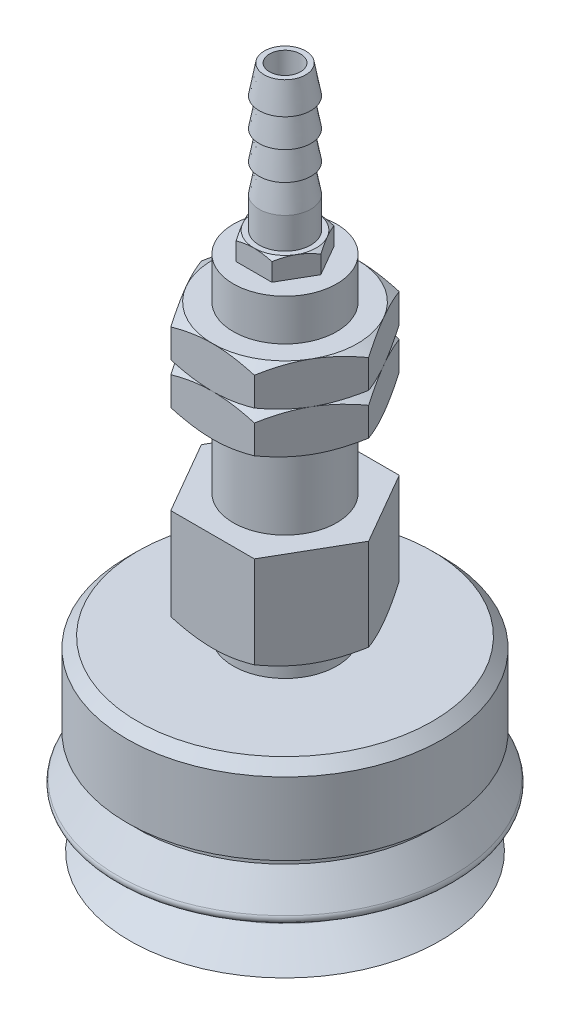
SolidWorks part; units mm, degrees
ref_plane "前视基准面" through (0, 0, 0) normal (0, 0, 1) x (1, 0, 0)
ref_plane "上视基准面" through (0, 0, 0) normal (0, 1, 0) x (1, 0, 0)
ref_plane "右视基准面" through (0, 0, 0) normal (1, 0, 0) x (0, 0, -1)
sketch "草图1" plane through (0, 0, 0) normal (0, 0, 1) x (1, 0, 0)
  line L0 (0, 17.9034) -> (0, 13.7034) construction
  line L1 (-2, 66) -> (2, 66)
  line L4 (-2.5, 63.25) -> (-2, 63.25)
  line L5 (-2.5, 63.25) -> (-2, 66)
  line L7 (14.25, 9) -> (14.25, 10)
  line L8 (14.25, 10) -> (15.25, 10)
  line L9 (-2.5, 60.5) -> (-2, 60.5)
  line L10 (-2.5, 60.5) -> (-2, 63.25)
  line L13 (-2.5, 57.75) -> (-2, 57.75)
  line L14 (15, 0) -> (11.1614, 2.7559)
  line L15 (-15, 0) -> (0, 0)
  line L16 (-2.5, 57.75) -> (-2, 60.5)
  line L19 (-2.5, 55) -> (-2, 57.75)
  line L22 (11.1614, 2.7559) -> (16.5, 5.6)
  line L23 (-5, 50) -> (5, 50)
  line L24 (13.8307, 4.1779) -> (13.6662, 4.4868) construction
  line L25 (-2.5, 55) -> (-2.5, 52)
  line L26 (-2.5, 52) -> (-3, 52)
  line L27 (2.5, 55) -> (2.5, 52)
  line L28 (-3, 52) -> (-3, 50)
  line L29 (2.5, 52) -> (3, 52)
  line L30 (3, 52) -> (3, 50)
  line L31 (-9.1506, 30) -> (0, 30) construction
  line L32 (-5, 18) -> (5, 18) construction
  line L33 (5, 50) -> (5, 46)
  line L34 (5, 46) -> (7, 46)
  line L35 (7, 46) -> (7, 42)
  line L48 (7, 42) -> (7, 38)
  line L49 (7, 38) -> (5, 38)
  line L50 (5, 38) -> (5, 30)
  line L51 (7, 30) -> (7, 20.5)
  line L52 (7, 20.5) -> (5, 20.5)
  line L61 (5, 20.5) -> (5, 18)
  line L62 (5, 30) -> (7, 30)
  line L63 (5, 18) -> (14.25, 18)
  line L64 (14.25, 18) -> (15.25, 17)
  line L65 (15.25, 17) -> (15.25, 10)
  line L68 (13.0807, 1.3779) -> (12.8766, 1.0937) construction
  line L69 (16.5, 5.6) -> (14.25, 9)
  line L71 (14.4922, 8) -> (0, 8)
  line L74 (10.5, 2.8) -> (14.4, 0)
  line L75 (14.4, 0) -> (15, 0)
  line L76 (14.4922, 8) -> (15.9958, 5.7279)
  line L77 (15.9958, 5.7279) -> (10.5, 2.8)
  line L78 (15.244, 6.8639) -> (15.5358, 7.057) construction
  line L79 (2.5, 55) -> (2, 57.75)
  line L80 (2.5, 57.75) -> (2, 60.5)
  line L81 (2.5, 57.75) -> (2, 57.75)
  line L82 (2.5, 60.5) -> (2, 63.25)
  line L83 (2.5, 60.5) -> (2, 60.5)
  line L84 (2.5, 63.25) -> (2, 66)
  line L85 (2.5, 63.25) -> (2, 63.25)
  point P10 (2.5, 63.949)
  point P14 (2.5, 61.949)
  point P18 (2.5, 59.949)
  point P55 (0, 0)
  point P71 (2.5, 18)
  dimension "D2" = 16
  dimension "D3" = 4
  dimension "D4" = 5
  dimension "D5" = 135
  dimension "D6" = 5.6
  dimension "D7" = 2.8
  dimension "D8" = 1
  dimension "D9" = 11
  dimension "D10" = 2
  dimension "D11" = 6
  dimension "D12" = 33
  dimension "D13" = 21
  dimension "D14" = 4
  dimension "D15" = 4
  dimension "D16" = 28.5
  dimension "S" = 14
  dimension "D17" = 4
  dimension "D18" = 1
  dimension "Y" = 8
  dimension "D20" = 2.5
  dimension "A" = 30
  dimension "D21" = 1
  dimension "D26" = 28.8
  dimension "B" = 66
  dimension "F" = 10
  dimension "J" = 20
  dimension "D" = 32
  dimension "E" = 14
  dimension "Z" = 5
sketch "草图2" plane through (0, 0, 0) normal (0, 0, 1) x (1, 0, 0)
  line L0 (-2, 66) -> (2, 66) construction
  line L8 (2.5, 55) -> (2.5, 52) construction
  line L9 (2.5, 52) -> (3, 52) construction
  line L10 (3, 52) -> (3, 50) construction
  line L11 (-5, 50) -> (5, 50) construction
  line L12 (5, 50) -> (5, 46) construction
  line L13 (5, 46) -> (7, 46) construction
  line L14 (7, 46) -> (7, 42) construction
  line L18 (7, 42) -> (7, 38) construction
  line L19 (7, 38) -> (5, 38) construction
  line L20 (5, 38) -> (5, 30) construction
  line L21 (5, 30) -> (7, 30) construction
  line L22 (7, 30) -> (7, 20.5) construction
  line L23 (7, 20.5) -> (5, 20.5) construction
  line L24 (5, 20.5) -> (5, 18) construction
  line L25 (5, 18) -> (14.25, 18) construction
  line L26 (14.25, 18) -> (15.25, 17) construction
  line L27 (15.25, 17) -> (15.25, 10) construction
  line L28 (2.5, 63.25) -> (2, 66) construction
  line L30 (0, 66) -> (2, 66)
  line L31 (2.5, 63.25) -> (2, 63.25) construction
  line L32 (2.5, 60.5) -> (2, 63.25) construction
  line L33 (2.5, 60.5) -> (2, 60.5) construction
  line L34 (2.5, 57.75) -> (2, 60.5) construction
  line L35 (2.5, 57.75) -> (2, 57.75) construction
  line L36 (2.5, 55) -> (2, 57.75) construction
  line L37 (14.25, 10) -> (15.25, 10) construction
  line L38 (2.5, 55) -> (2.5, 52)
  line L39 (2.5, 52) -> (3, 52)
  line L40 (3, 52) -> (3, 50)
  line L41 (3, 50) -> (5, 50)
  line L42 (5, 50) -> (5, 46)
  line L43 (5, 46) -> (7, 46)
  line L44 (7, 46) -> (7, 42)
  line L45 (14.25, 9) -> (14.25, 10) construction
  line L46 (16.5, 5.6) -> (14.25, 9) construction
  line L47 (11.1614, 2.7559) -> (16.5, 5.6) construction
  line L48 (7, 42) -> (7, 38)
  line L49 (7, 38) -> (5, 38)
  line L50 (5, 38) -> (5, 30)
  line L51 (5, 30) -> (7, 30)
  line L52 (7, 30) -> (7, 20.5)
  line L53 (7, 20.5) -> (5, 20.5)
  line L54 (5, 20.5) -> (5, 18)
  line L55 (5, 18) -> (14.25, 18)
  line L56 (14.25, 18) -> (15.25, 17)
  line L57 (15.25, 17) -> (15.25, 10)
  line L58 (15, 0) -> (11.1614, 2.7559) construction
  line L59 (14.4, 0) -> (15, 0) construction
  line L60 (0, 66) -> (0, 8)
  line L61 (10.5, 2.8) -> (14.4, 0) construction
  line L62 (15.9958, 5.7279) -> (10.5, 2.8) construction
  line L63 (14.4922, 8) -> (15.9958, 5.7279) construction
  line L64 (14.4922, 8) -> (0, 8) construction
  line L65 (2.5, 63.25) -> (2, 66)
  line L66 (2.5, 63.25) -> (2, 63.25)
  line L67 (2.5, 60.5) -> (2, 63.25)
  line L68 (2.5, 60.5) -> (2, 60.5)
  line L69 (2.5, 57.75) -> (2, 60.5)
  line L70 (2.5, 57.75) -> (2, 57.75)
  line L71 (2.5, 55) -> (2, 57.75)
  line L72 (14.25, 10) -> (15.25, 10)
  line L73 (14.25, 9) -> (14.25, 10)
  line L74 (16.1965, 6.0586) -> (14.25, 9)
  line L75 (11.8715, 3.1342) -> (16.0146, 5.3414)
  line L76 (15, 0) -> (11.8149, 2.2867)
  line L77 (14.4, 0) -> (15, 0)
  line L78 (11.1535, 2.3308) -> (14.4, 0)
  line L79 (15.5104, 5.4693) -> (11.21, 3.1783)
  line L80 (14.4922, 8) -> (15.6923, 6.1865)
  line L81 (14.4922, 8) -> (0, 8)
  arc A0 (16.1965, 6.0586) -> (16.0146, 5.3414) centre (15.7795, 5.7827) cw
  arc A1 (15.5104, 5.4693) -> (15.6923, 6.1865) centre (15.2753, 5.9106) ccw
  arc A2 (11.1535, 2.3308) -> (11.21, 3.1783) centre (11.4451, 2.737) cw
  arc A3 (11.8715, 3.1342) -> (11.8149, 2.2867) centre (12.1065, 2.6929) ccw
  dimension "D1" = 0.5
revolve "旋转1" add sketch "草图2" angle 360 about L0
cosmetic thread "装饰螺纹线1" parameters "D2"=8.6
cosmetic thread "装饰螺纹线3" parameters "D2"=8.6
sketch "草图4" plane through (0, 52, 0) normal (0, 1, 0) x (1, 0, 0)
  line L1 (1.7321, -3) -> (3.4641, 0)
  line L2 (3.4641, 0) -> (1.7321, 3)
  line L3 (1.7321, 3) -> (-1.7321, 3)
  line L4 (-1.7321, 3) -> (-3.4641, 0)
  line L5 (-3.4641, 0) -> (-1.7321, -3)
  line L6 (-1.7321, -3) -> (1.7321, -3)
  circle A0 centre (0, 0) radius 3
  circle A1 centre (0, 0) radius 3 construction
extrude "凸台-拉伸1" add sketch "草图4" against normal up to vertex (2 mm away) from vertex separate body contours L4 L5 L6 L1 L2 L3 up to point (-3, 50, 0) starting at point (-3, 52, 0)
extrude "切除-拉伸1" cut sketch "草图4<3>" against normal up to vertex (2 mm away) draft 60 from vertex flip side to cut contours A0 up to point (-1.732, 50, 3) starting at point (-1.732, 52, 3)
sketch "草图4<3>" plane through (0, 52, 0) normal (0, 1, 0) x (1, 0, 0) same geometry as "草图4"
sketch "草图5" plane through (0, 46, 0) normal (0, 1, 0) x (1, 0, 0)
  line L1 (-4.0415, 7) -> (-8.0829, 0)
  line L2 (-8.0829, 0) -> (-4.0415, -7)
  line L3 (-4.0415, -7) -> (4.0415, -7)
  line L4 (4.0415, -7) -> (8.0829, 0)
  line L5 (8.0829, 0) -> (4.0415, 7)
  line L6 (4.0415, 7) -> (-4.0415, 7)
  circle A0 centre (0, 0) radius 7
  circle A1 centre (0, 0) radius 7 construction
extrude "凸台-拉伸2" add sketch "草图5" against normal up to vertex (4 mm away) from vertex separate body contours L4 L5 L6 L1 L2 L3 up to point (7, 42, 0) starting at point (7, 46, 0)
extrude "凸台-拉伸3" add sketch "草图5<3>" against normal up to vertex (8 mm away) from vertex separate body contours L4 L5 L6 L1 L2 L3 up to point (7, 38, 0) starting at point (7, 42, 0)
sketch "草图5<3>" plane through (0, 46, 0) normal (0, 1, 0) x (1, 0, 0) same geometry as "草图5"
extrude "切除-拉伸2" cut sketch "草图5<4>" against normal up to vertex (4 mm away) draft 60 from vertex flip side to cut contours A0 up to point (4.0415, 42, 7) starting at point (4.0415, 46, 7)
sketch "草图5<4>" plane through (0, 46, 0) normal (0, 1, 0) x (1, 0, 0) same geometry as "草图5"
extrude "切除-拉伸3" cut sketch "草图5<5>" along normal up to vertex (-0.6252 mm away) draft 60 from vertex flip side to cut contours A0 up to point (-4.0415, 45.3748, 7) starting at point (-4.0415, 42, 7)
sketch "草图5<5>" plane through (0, 46, 0) normal (0, 1, 0) x (1, 0, 0) same geometry as "草图5"
extrude "切除-拉伸4" cut sketch "草图5<6>" against normal up to vertex (8 mm away) draft 60 from vertex flip side to cut contours A0 up to point (-4.0415, 38, 7) starting at point (-4.0415, 42, 7)
sketch "草图5<6>" plane through (0, 46, 0) normal (0, 1, 0) x (1, 0, 0) same geometry as "草图5"
extrude "切除-拉伸5" cut sketch "草图5<7>" along normal up to vertex (-4.6252 mm away) draft 60 from vertex flip side to cut contours A0 up to point (-4.0415, 41.3748, 7) starting at point (-4.0415, 38, 7)
sketch "草图5<7>" plane through (0, 46, 0) normal (0, 1, 0) x (1, 0, 0) same geometry as "草图5"
sketch "草图6" plane through (0, 30, 0) normal (0, 1, 0) x (1, 0, 0)
  line L0 (-5, 0) -> (5, 0) construction
  line L1 (4.0415, 7) -> (-4.0415, 7)
  line L2 (-4.0415, 7) -> (-8.0829, 0)
  line L3 (-8.0829, 0) -> (-4.0415, -7)
  line L4 (-4.0415, -7) -> (4.0415, -7)
  line L5 (4.0415, -7) -> (8.0829, 0)
  line L6 (8.0829, 0) -> (4.0415, 7)
  circle A0 centre (0, 0) radius 7
  circle A1 centre (0, 0) radius 7 construction
extrude "凸台-拉伸4" add sketch "草图6" against normal up to vertex (9.5 mm away) from vertex separate body contours L5 L6 L1 L2 L3 L4 up to point (7, 20.5, 0) starting at point (7, 30, 0)
sketch "草图8" plane through (0, 66, 0) normal (0, 1, 0) x (1, 0, 0)
  circle A0 centre (0, 0) radius 1.5
  dimension "D1" = 3
extrude "切除-拉伸9" cut sketch "草图6<5>" along normal blind 10 draft 60 from vertex flip side to cut contours A0 starting at point (7, 20.5, 0)
sketch "草图6<5>" plane through (0, 30, 0) normal (0, 1, 0) x (1, 0, 0) same geometry as "草图6"
combine bodies "组合1" operation type add bodies to combine 109 116 118 112 125
extrude "切除-拉伸8" cut sketch "草图8" along normal through all from vertex starting at point (-3, 50, 0)
sketch "草图9" plane through (0, 0, 0) normal (0, 0, 1) x (1, 0, 0)
  line L0 (7, 30) -> (7, 20.5) construction
  line L1 (0, 8) -> (2.15, 8)
  line L2 (0, 8) -> (0, 25.25)
  line L3 (0, 25.25) -> (2.15, 25.25)
  line L4 (2.15, 8) -> (2.15, 25.25)
  line L6 (0, 84.7063) -> (0, -15.8269) construction
  point P7 (7, 25.25)
  dimension "D1" = 4.3
revolve "切除-旋转1" cut sketch "草图9" angle 360 about L6
cosmetic thread "装饰螺纹线4" parameters "D2"=5
